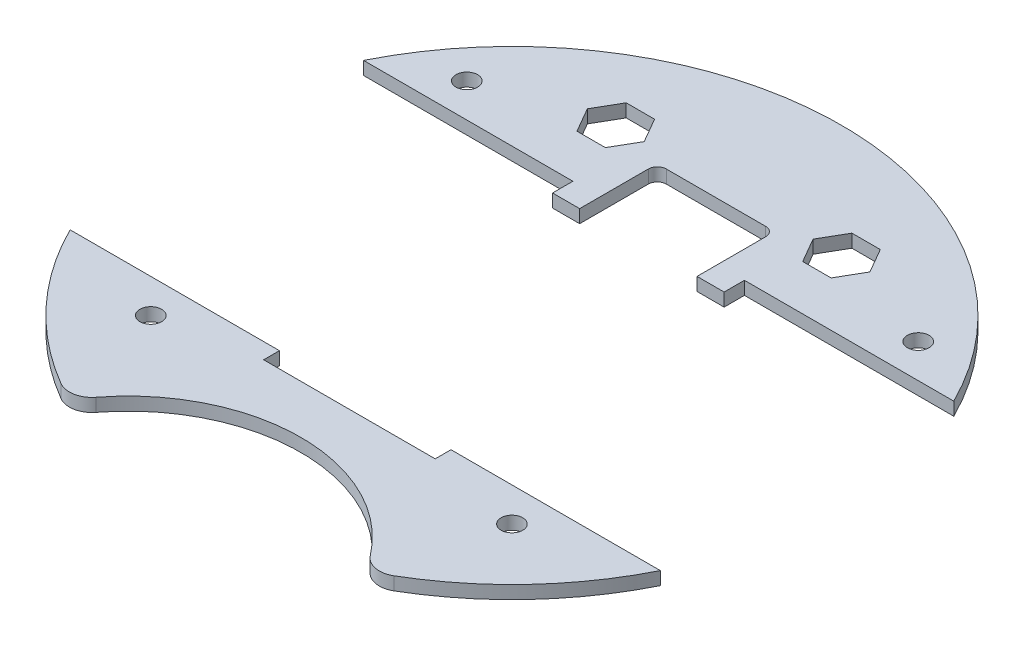
SolidWorks part; units mm, degrees
material "Acrylic (Medium-high impact)"
ref_plane "Front Plane" through (0, 0, 0) normal (0, 0, 1) x (1, 0, 0)
ref_plane "Top Plane" through (0, 0, 0) normal (0, 1, 0) x (1, 0, 0)
ref_plane "Right Plane" through (0, 0, 0) normal (1, 0, 0) x (0, 0, -1)
sketch "Sketch1" plane through (0, 0, 0) normal (0, 1, 0) x (1, 0, 0)
  line L0 (0, -85) -> (-32.7511, -65.2408) construction
  line L1 (0, -85) -> (0, 0) construction
  arc A0 (36.8566, -63.0126) -> (-36.8566, -63.0126) centre (0, 0) ccw
  arc A1 (30.3631, -61.7375) -> (-30.3631, -61.7375) centre (0, -85) ccw
  arc A2 (-30.3631, -61.7375) -> (-36.8566, -63.0126) centre (-34.3322, -58.6967) cw
  arc A3 (36.8566, -63.0126) -> (30.3631, -61.7375) centre (34.3322, -58.6967) cw
  dimension "D1" = 146
  dimension "D2" = 76.5
  dimension "D4" = 5
  dimension "D3" = 85
extrude "Boss-Extrude1" add sketch "Sketch1" along normal blind 2.9
sketch "solenoid placement" plane through (0, 2.9, 0) normal (0, 1, 0) x (1, 0, 0)
  line L4 (-19, -36) -> (19, -36)
  line L5 (-19, 28) -> (-19, -36)
  line L6 (19, 28) -> (-19, 28)
  line L7 (19, -36) -> (19, 28)
  line L8 (-19, -36) -> (19, -36)
  line L9 (-19, 28) -> (-19, -36)
  line L10 (19, 28) -> (-19, 28)
  line L11 (19, -36) -> (19, 28)
  dimension "D1" = 0
extrude "Cut-Extrude1" cut sketch "solenoid placement" against normal through all
sketch "Sketch4" plane through (0, 2.9, 0) normal (0, 1, 0) x (1, 0, 0)
  line L4 (-13, 28) -> (13, 28)
  line L5 (13, 28) -> (13, 43.2)
  line L6 (11, 45.2) -> (-11, 45.2)
  line L7 (-13, 43.2) -> (-13, 28)
  line L8 (-13, 28) -> (13, 28)
  line L9 (13, 28) -> (13, 43.2)
  line L10 (11, 45.2) -> (-11, 45.2)
  line L11 (-13, 43.2) -> (-13, 28)
  arc A2 (13, 43.2) -> (11, 45.2) centre (11, 43.2) ccw
  arc A3 (-11, 45.2) -> (-13, 43.2) centre (-11, 43.2) ccw
  arc A4 (13, 43.2) -> (11, 45.2) centre (11, 43.2) ccw
  arc A5 (-11, 45.2) -> (-13, 43.2) centre (-11, 43.2) ccw
  dimension "D1" = 0
extrude "Cut-Extrude4" cut sketch "Sketch4" against normal through all
sketch "Sketch5" plane through (0, 2.9, 0) normal (0, 1, 0) x (1, 0, 0)
  line L6 (-18.7069, 48) -> (-21.8534, 53.45)
  line L7 (-21.8534, 53.45) -> (-28.1466, 53.45)
  line L8 (-28.1466, 53.45) -> (-31.2931, 48)
  line L9 (-31.2931, 48) -> (-28.1466, 42.55)
  line L10 (-28.1466, 42.55) -> (-21.8534, 42.55)
  line L11 (-21.8534, 42.55) -> (-18.7069, 48)
  line L12 (-18.7069, 48) -> (-21.8534, 53.45)
  line L13 (-21.8534, 53.45) -> (-28.1466, 53.45)
  line L14 (-28.1466, 53.45) -> (-31.2931, 48)
  line L15 (-31.2931, 48) -> (-28.1466, 42.55)
  line L16 (-28.1466, 42.55) -> (-21.8534, 42.55)
  line L17 (-21.8534, 42.55) -> (-18.7069, 48)
  line L18 (18.7069, 48) -> (21.8534, 42.55)
  line L19 (21.8534, 53.45) -> (18.7069, 48)
  line L20 (28.1466, 53.45) -> (21.8534, 53.45)
  line L21 (31.2931, 48) -> (28.1466, 53.45)
  line L22 (28.1466, 42.55) -> (31.2931, 48)
  line L23 (21.8534, 42.55) -> (28.1466, 42.55)
  line L24 (18.7069, 48) -> (21.8534, 42.55)
  line L25 (21.8534, 53.45) -> (18.7069, 48)
  line L26 (28.1466, 53.45) -> (21.8534, 53.45)
  line L27 (31.2931, 48) -> (28.1466, 53.45)
  line L28 (28.1466, 42.55) -> (31.2931, 48)
  line L29 (21.8534, 42.55) -> (28.1466, 42.55)
  dimension "D1" = 0
  dimension "D2" = 0
extrude "Cut-Extrude5" cut sketch "Sketch5" against normal through all
sketch "Sketch6" plane through (0, 2.9, 0) normal (0, 1, 0) x (1, 0, 0)
  circle A1 centre (40, -40) radius 2.4
  circle A2 centre (40, -40) radius 2.4
  circle A3 centre (-40, -40) radius 2.4
  circle A4 centre (-40, -40) radius 2.4
  circle A5 centre (-50, 40) radius 2.4
  circle A6 centre (-50, 40) radius 2.4
  circle A7 centre (50, 40) radius 2.4
  circle A8 centre (50, 40) radius 2.4
  dimension "D1" = 0
  dimension "D2" = 0
  dimension "D3" = 0
  dimension "D4" = 0
extrude "Cut-Extrude6" cut sketch "Sketch6" against normal through all
sketch "Sketch3" plane through (0, 2.9, 0) normal (0, 1, 0) x (1, 0, 0)
  line L0 (-19, 28) -> (-19, 32.5)
  line L1 (73, -32.5) -> (-73, -32.5)
  line L2 (73, -32.5) -> (73, 32.5)
  line L3 (73, 32.5) -> (19, 32.5)
  line L4 (-73, -32.5) -> (-73, 32.5)
  line L5 (73, -32.5) -> (-73, 32.5) construction
  line L6 (73, 32.5) -> (-73, -32.5) construction
  line L7 (-19, 28) -> (19, 28)
  line L8 (19, 28) -> (19, 32.5)
  line L9 (-19, 32.5) -> (-73, 32.5)
  line L10 (-19, 28) -> (-19, -36) construction
  line L11 (-13, 28) -> (-19, 28) construction
  arc A0 (36.8566, -63.0126) -> (-36.8566, -63.0126) centre (0, 0) ccw construction
  point P0 (0, 0)
  dimension "D1" = 65
extrude "Cut-Extrude3" cut sketch "Sketch3" against normal through all
equation "\"smallPulleyTeeth\"= 15"
equation "\"largePulleyTeeth\"= 30"
equation "\"eighthThick\"= 2.9mm"
equation "\"sixteenthThick\" = 1.7mm"
equation "\"quarterThick\"=6.0mm"
equation "\"OD\" = 146mm"
equation "\"puckAngle\" = 60.5deg"
equation "\"D1@Sketch1\"=\"OD\""
equation "\"puckDiam\" = 76.5mm"
equation "\"D2@Sketch1\"=\"puckDiam\""
equation "\"D1@Boss-Extrude1\"=\"eighthThick\""
equation "\"axlePress\" = 5.9mm"
equation "\"press\" = 0.2mm"
equation "\"wheelClear\" = 0.3mm"
equation "\"10-32clear\" = 4.8mm"
equation "\"6-32clear\" = 3.3mm"
equation "\"8-32clear\" = 4.0mm"
equation "\"wheelHeight\" = 22mm"
equation "\"wheelWell\" = 65mm"
equation "\"D1@Sketch3\"=\"wheelWell\""
equation "\"puckDist\" = 85mm"
equation "\"scoopFillet\" = 5mm"
equation "\"4-40clear\" = 3.0mm"
equation "\"D3@Sketch1\"=\"puckDist\""
equation "\"D4@Sketch1\"=\"scoopFillet\""
